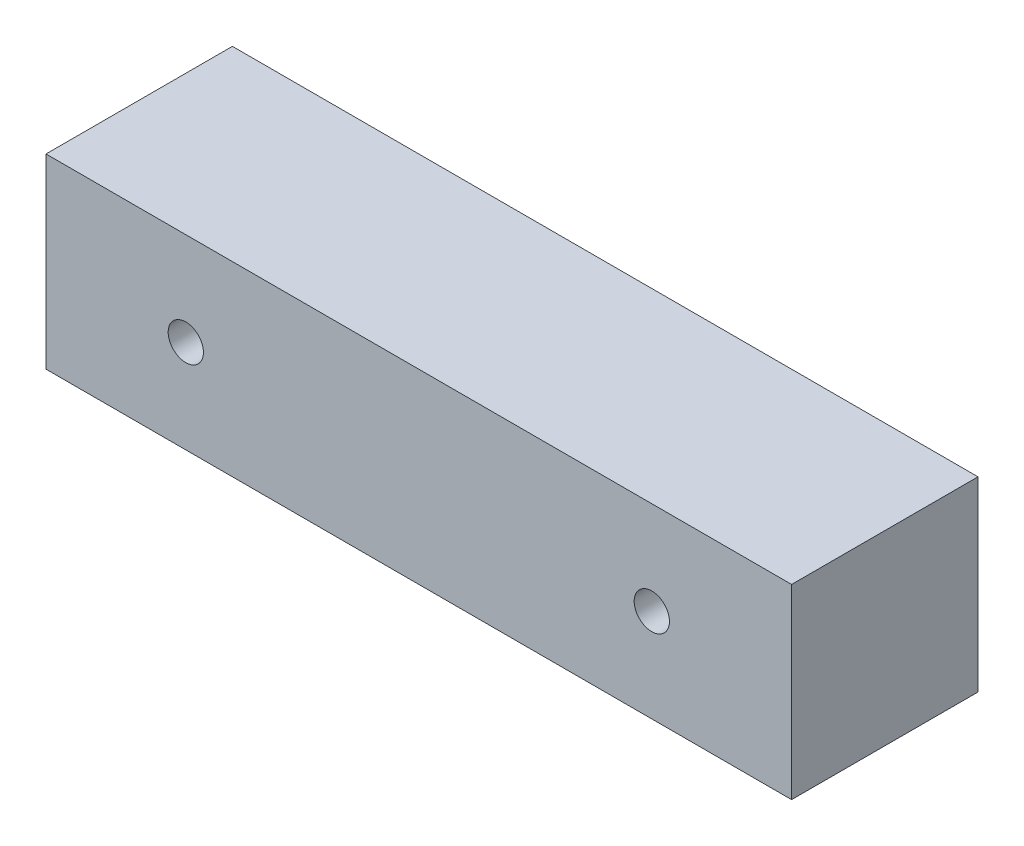
SolidWorks part; units mm, degrees
ref_plane "Alzado" through (0, 0, 0) normal (0, 0, 1) x (1, 0, 0)
ref_plane "Planta" through (0, 0, 0) normal (0, 1, 0) x (1, 0, 0)
ref_plane "Vista lateral" through (0, 0, 0) normal (1, 0, 0) x (0, 0, -1)
sketch "Croquis1" plane through (0, 0, 0) normal (0, 0, 1) x (1, 0, 0)
  line L0 (40, 0) -> (-40, 0) construction
  line L1 (-40, 10) -> (40, 10)
  line L2 (40, 10) -> (40, -10)
  line L3 (40, -10) -> (-40, -10)
  line L4 (-40, -10) -> (-40, 10)
  line L5 (0, 0) -> (0, -3.7626) construction
  circle A0 centre (25, 0) radius 1.8929
  circle A1 centre (-25, 0) radius 1.8929
  point P4 (0, 0)
  point P7 (-40, 0)
  dimension "D1" = 80
  dimension "D2" = 20
  dimension "D3" = 15
extrude "Saliente-Extruir1" add sketch "Croquis1" along normal blind 20
sketch "Croquis2" plane through (0, 0, 20) normal (0, 0, 1) x (1, 0, 0)
  line L0 (0, 0) -> (0, 5.7256) construction
  line L7 (20, -10) -> (40, -10)
  line L8 (20, 10) -> (20, -10)
  line L9 (40, 10) -> (20, 10)
  line L10 (40, -10) -> (40, 10)
  dimension "D1" = 20
extrude "Cortar-Extruir1" [suppressed] cut sketch "Croquis2" against normal blind 10
sketch "Croquis3" plane through (0, 0, 0) normal (0, 0, -1) x (-1, 0, 0)
  line L0 (40, 10) -> (20, 10)
  line L1 (-40, 10) -> (40, 10) construction
  line L2 (20, 10) -> (20, -10)
  line L3 (40, -10) -> (-40, -10) construction
  line L4 (20, -10) -> (40, -10)
  line L5 (40, -10) -> (40, 10)
  line L6 (-20, 10) -> (-20, -10)
  line L7 (-20, -10) -> (-40, -10)
  line L8 (-40, -10) -> (-40, 10)
  line L9 (-40, 10) -> (-20, 10)
  dimension "D1" = 20
  dimension "D2" = 20
extrude "Cortar-Extruir2" [suppressed] cut sketch "Croquis3" against normal blind 10
